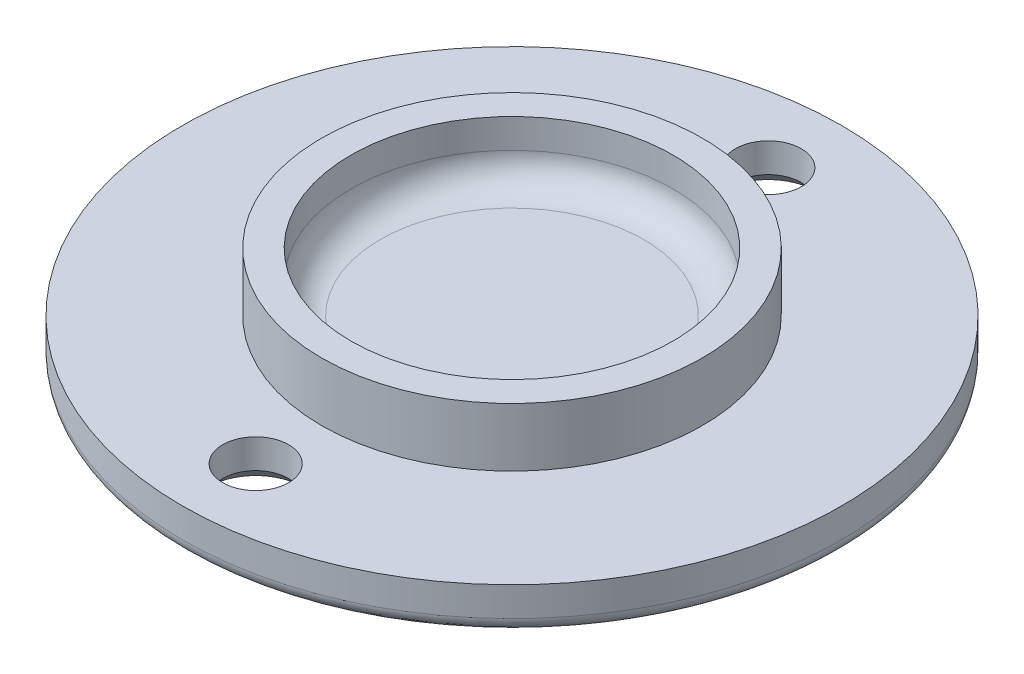
SolidWorks part; units mm, degrees
ref_plane "Front Plane" through (0, 0, 0) normal (0, 0, 1) x (1, 0, 0)
ref_plane "Top Plane" through (0, 0, 0) normal (0, 1, 0) x (1, 0, 0)
ref_plane "Right Plane" through (0, 0, 0) normal (1, 0, 0) x (0, 0, -1)
ref_axis "X" through (88.99, 0, 0) along (-1, 0, 0)
ref_axis "Y" through (0, 55, 0) along (0, -1, 0)
ref_axis "Z" through (0, 0, -88.99) along (0, 0, 1)
sketch "Sketch1" plane through (0, 0, 0) normal (0, 0, 1) x (1, 0, 0)
  line L0 (0, 0) -> (0, -21.8723) construction
  line L4 (-22.5, 0) -> (-22.5, 3)
  line L5 (-22.5, 3) -> (-13, 3)
  line L7 (-11, 3) -> (0, 3)
  line L8 (0, 3) -> (0, 0)
  line L9 (0, 0) -> (-22.5, 0)
  line L10 (-13, 3) -> (-13, 7)
  line L11 (-13, 7) -> (-11, 7)
  line L12 (-11, 7) -> (-11, 3)
  dimension "D1" = 45
  dimension "D2" = 2
  dimension "D3" = 3
  dimension "D4" = 3
  dimension "D5" = 13
  dimension "D6" = 4
revolve "Revolve1" add sketch "Sketch1" angle 360 about L0
hole_wizard "M4 Clearance Hole1" positions "Sketch2" profile "Sketch3" hole size "M4" standard "DIN" end condition up to next
sketch "Sketch2" plane through (0, 3, 0) normal (0, 1, 0) x (1, 0, 0)
  circle A0 centre (0, 0) radius 17.5
  point P5 (0, 17.5)
  point P9 (0, -17.5)
  dimension "D1" = 35
sketch "Sketch3" plane through (0, 3, 17.5) normal (1, 0, 0) x (0, 0, 1)
  line L0 (0, 0) -> (0, 3)
  line L1 (0, 3) -> (2.25, 3)
  line L2 (2.25, 3) -> (2.25, 0)
  line L5 (2.25, 0) -> (0, 0)
  line L11 (0, -6.35) -> (0, 107.95) construction
  dimension "Thru Hole Dia." = 4.5
  dimension "Thru Hole Depth" = 3
sketch "Sketch4" plane through (0, 3, 0) normal (0, 1, 0) x (1, 0, 0)
  circle A0 centre (0, 0) radius 7
  dimension "D1" = 14
extrude "Cut-Extrude1" [suppressed] cut sketch "Sketch4" against normal through all
fillet "Fillet1" radius 2 1 edges at (0, 3, 11)
fillet "Fillet2" radius 1 1 edges at (0, 0, 22.5)
chamfer "Chamfer1" distance 1 angle 45 2 edges at (0, 0, -19.75) (0, 0, 15.25)
